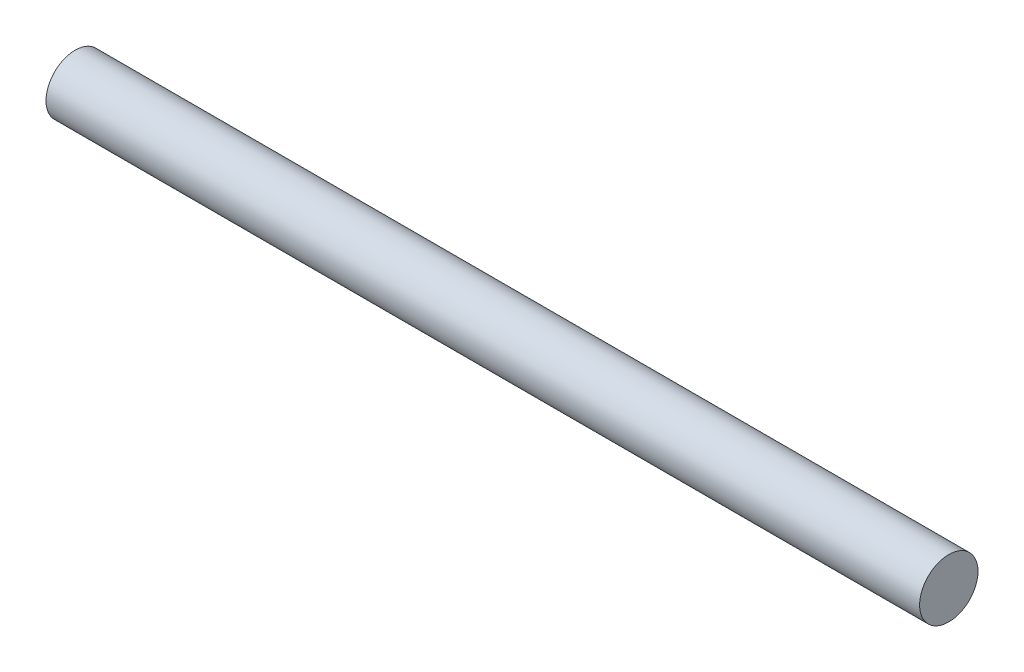
SolidWorks part; units mm, degrees
ref_plane "Front Plane" through (0, 0, 0) normal (0, 0, 1) x (1, 0, 0)
ref_plane "Top Plane" through (0, 0, 0) normal (0, 1, 0) x (1, 0, 0)
ref_plane "Right Plane" through (0, 0, 0) normal (1, 0, 0) x (0, 0, -1)
sketch "Sketch1" plane through (0, 0, 0) normal (1, 0, 0) x (0, 0, -1)
  circle A0 centre (0, 0) radius 12.7
  dimension "D1" = 25.4
extrude "Boss-Extrude1" add sketch "Sketch1" along normal blind 175 and the other way blind 175
sketch "Sketch2" plane through (175, 0, 0) normal (1, 0, 0) x (0, 0, -1)
  circle A0 centre (0, 0) radius 12.7 construction
  circle A1 centre (0, 0) radius 12.7
extrude "Boss-Extrude2" add sketch "Sketch2" along normal blind 15
sketch "Sketch3" plane through (-175, 0, 0) normal (-1, 0, 0) x (0, 0, 1)
  circle A1 centre (0, 0) radius 12.7
  circle A2 centre (0, 0) radius 12.7
  dimension "D1" = 0
extrude "Boss-Extrude3" add sketch "Sketch3" along normal blind 15
